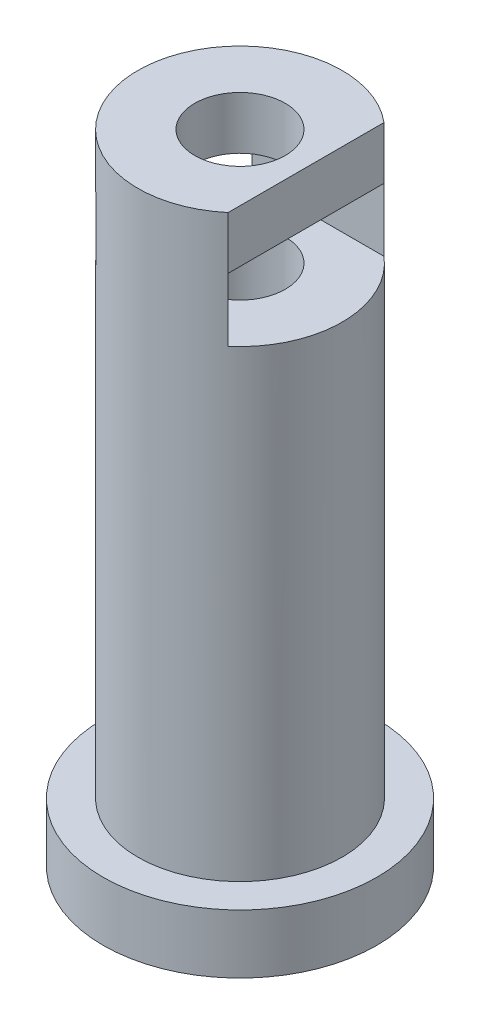
SolidWorks part; units mm, degrees
ref_plane "Front Plane" through (0, 0, 0) normal (0, 0, 1) x (1, 0, 0)
ref_plane "Top Plane" through (0, 0, 0) normal (0, 1, 0) x (1, 0, 0)
ref_plane "Right Plane" through (0, 0, 0) normal (1, 0, 0) x (0, 0, -1)
sketch "Sketch1" plane through (0, 0, 0) normal (0, 1, 0) x (1, 0, 0)
  circle A0 centre (0, 0) radius 6.5
  circle A1 centre (0, 0) radius 4.85
  circle A2 centre (0, 0) radius 3
  circle A3 centre (0, 0) radius 2.15
  dimension "D1" = 9.7
  dimension "D2" = 13
  dimension "D3" = 6
  dimension "D4" = 4.3
extrude "Boss-Extrude1" add sketch "Sketch1" along normal blind 27.5 contours A1 A2 | A2 A3 | A3 region at (-4.7128, 0, 0) region at (-2.9151, 0, 0) region at (0, 0, 0)
extrude "Boss-Extrude2" add sketch "Sketch1<3>" against normal blind 2.8 contours A0 A1 | A1 A2 | A2 A3 | A3 region at (-6.3162, 0, 0) region at (-4.7128, 0, 0) region at (-2.9151, 0, 0) region at (0, 0, 0)
sketch "Sketch1<3>" plane through (0, 0, 0) normal (0, 1, 0) x (1, 0, 0) same geometry as "Sketch1"
sketch "Sketch2" plane through (0, 0, 0) normal (0, 1, 0) x (1, 0, 0)
  line L0 (2.1362, 3.7) -> (9.7215, 3.7)
  line L1 (4.2724, 0) -> (2.1362, 3.7)
  line L2 (2.1362, 3.7) -> (-2.1362, 3.7)
  line L3 (-2.1362, 3.7) -> (-4.2724, 0)
  line L4 (-4.2724, 0) -> (-2.1362, -3.7)
  line L5 (-2.1362, -3.7) -> (2.1362, -3.7)
  line L6 (2.1362, -3.7) -> (4.2724, 0)
  line L7 (2.1362, -3.7) -> (9.7215, -3.7)
  line L8 (9.7215, -3.7) -> (9.7215, 3.7)
  line L9 (3.1357, 3.7) -> (3.1357, -3.7)
  line L10 (-2.1362, 3.7) -> (-7.5163, 3.7)
  line L11 (-7.5163, 3.7) -> (-7.5163, -3.7)
  line L12 (-7.5163, -3.7) -> (-2.1362, -3.7)
  circle A0 centre (0, 0) radius 3.7 construction
  circle A1 centre (0, 0) radius 4.85
  circle A2 centre (0, 0) radius 4.85
  circle A3 centre (0, 0) radius 2.15
  dimension "D3" = 4.3
  dimension "D2" = 7.4
  dimension "D1" = 0
extrude "Cut-Extrude1" cut sketch "Sketch2" against normal blind 3 from offset 25 contours L5 L6 L1 L2 L3 L4 A3 | A2 L7 L8 L0 | L7 A2 L0 L1 L6 | L9 L0 L1 | L9 L6 L7 | L1 L9 L6 | A2 L10 L11 L12 | L10 A2 L12 L4 L3 region at (2.8025, 0, -3.1229) region at (2.5453, 0, -2.7821) region at (4.3317, 0, -2.007) region at (7.0013, 0, 0) region at (3.5146, 0, 0) region at (-3.2726, 0, -1.8894) region at (-5.8832, 0, 0) region at (2.8025, 0, 3.1229)
extrude "Cut-Extrude2" cut sketch "Sketch2<3>" against normal blind 15 from surface contours A3 region at (0, 0, 0) starting at face at (0, 27.5, 4.85)
sketch "Sketch2<3>" plane through (0, 0, 0) normal (0, 1, 0) x (1, 0, 0) same geometry as "Sketch2"
extrude "Cut-Extrude3" cut sketch "Sketch2<4>" along normal blind 15 from surface contours L1 L9 L6 | L9 A2 L1 L6 region at (4.3317, 0, -2.007) region at (3.5146, 0, 0) starting at face at (0, 22, 2.15)
sketch "Sketch2<4>" plane through (0, 0, 0) normal (0, 1, 0) x (1, 0, 0) same geometry as "Sketch2"
sketch "Sketch3" plane through (0, 0, 0) normal (0, 1, 0) x (1, 0, 0)
  circle A0 centre (0, 0) radius 2.35
  dimension "D1" = 4.7
extrude "Cut-Extrude4" cut sketch "Sketch3" along normal blind 1 from surface starting at face at (0, -2.8, 6.5)
